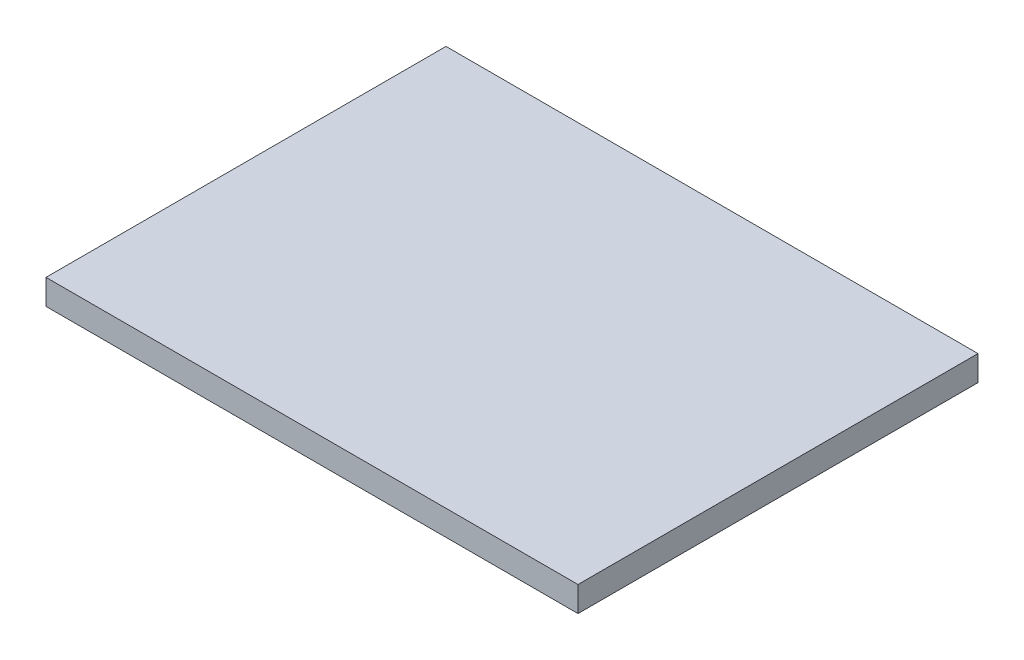
SolidWorks part; units mm, degrees
ref_plane "Front Plane" through (0, 0, 0) normal (0, 0, 1) x (1, 0, 0)
ref_plane "Top Plane" through (0, 0, 0) normal (0, 1, 0) x (1, 0, 0)
ref_plane "Right Plane" through (0, 0, 0) normal (1, 0, 0) x (0, 0, -1)
sketch "Sketch1" plane through (0, 0, 0) normal (0, 1, 0) x (1, 0, 0)
  line L1 (-16.891, -12.7) -> (16.891, -12.7)
  line L2 (-16.891, -12.7) -> (-16.891, 12.7)
  line L3 (-16.891, 12.7) -> (16.891, 12.7)
  line L4 (16.891, -12.7) -> (16.891, 12.7)
  line L5 (-16.891, -12.7) -> (16.891, 12.7) construction
  line L6 (-16.891, 12.7) -> (16.891, -12.7) construction
  point P0 (0, 0)
  dimension "D1" = 25.4
  dimension "D2" = 33.782
extrude "Boss-Extrude1" add sketch "Sketch1" along normal blind 1.6
